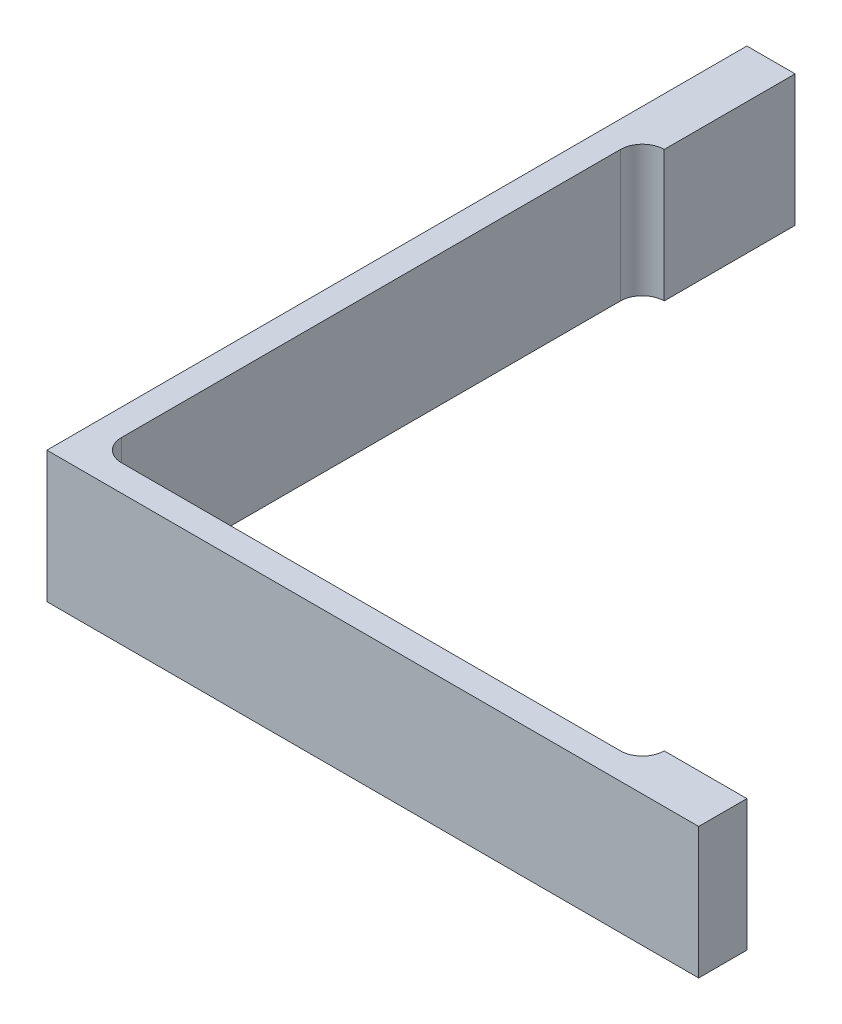
SolidWorks part; units mm, degrees
ref_plane "Front Plane" through (0, 0, 0) normal (0, 0, 1) x (1, 0, 0)
ref_plane "Top Plane" through (0, 0, 0) normal (0, 1, 0) x (1, 0, 0)
ref_plane "Right Plane" through (0, 0, 0) normal (1, 0, 0) x (0, 0, -1)
sketch "Sketch1" plane through (0, 0, 0) normal (0, 1, 0) x (1, 0, 0)
  line L0 (0, 0) -> (0, 50.8)
  line L2 (3.5, 50.8) -> (3.5, 3.5)
  line L3 (3.5, 3.5) -> (47.3, 3.5)
  line L5 (47.3, 0) -> (0, 0)
  line L6 (0, 50.8) -> (3.5, 50.8)
  line L7 (47.3, 0) -> (47.3, 3.5)
  dimension "D1" = 3.5
  dimension "D2" = 50.8
  dimension "D3" = 47.3
  dimension "D5" = 3.5
extrude "Boss-Extrude1" add sketch "Sketch1" along normal blind 9.525
sketch "Sketch2" plane through (0, 9.525, 0) normal (0, 1, 0) x (1, 0, 0)
  line L0 (3.5, 3.5) -> (3.5, 50.8) construction
  line L1 (3.5, 41.3) -> (1.9125, 41.3)
  line L2 (3.5, 41.3) -> (3.5, 3.5)
  line L4 (1.9125, 41.3) -> (1.9125, 3.5)
  line L5 (47.3, 3.5) -> (3.5, 3.5) construction
  line L6 (3.5, 3.5) -> (41.3, 3.5)
  line L7 (1.9125, 3.5) -> (1.9125, 1.9125)
  line L8 (1.9125, 1.9125) -> (41.3, 1.9125)
  line L9 (41.3, 3.5) -> (41.3, 1.9125)
  dimension "D1" = 9.5
  dimension "D4" = 6
  dimension "D5" = 1.5875
extrude "Cut-Extrude1" cut sketch "Sketch2" against normal through all
fillet "Fillet1" radius 1.5875 3 edges at (41.3, 4.7625, -1.9125) (1.9125, 4.7625, -1.9125) (1.9125, 4.7625, -41.3)
